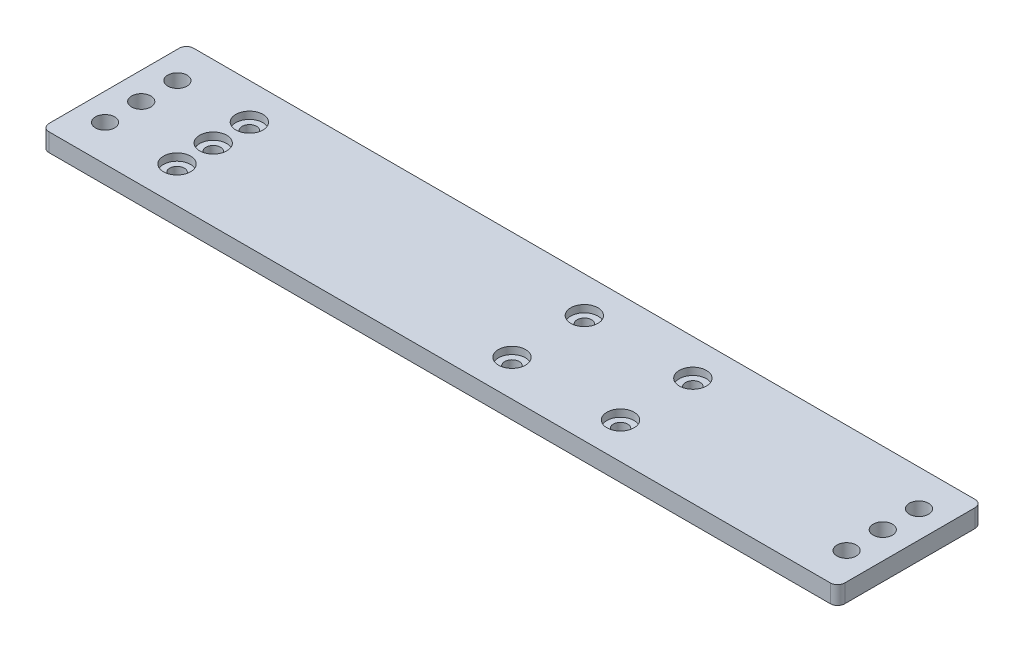
SolidWorks part; units mm, degrees
ref_plane "Front" through (0, 0, 0) normal (0, 0, 1) x (1, 0, 0)
ref_plane "Top" through (0, 0, 0) normal (0, 1, 0) x (1, 0, 0)
ref_plane "Right" through (0, 0, 0) normal (1, 0, 0) x (0, 0, -1)
sketch "Sketch1" plane through (0, 0, 0) normal (0, 1, 0) x (1, 0, 0)
  line L1 (-139.7, -25.4) -> (139.7, -25.4)
  line L2 (-139.7, -25.4) -> (-139.7, 25.4)
  line L3 (-139.7, 25.4) -> (139.7, 25.4)
  line L4 (139.7, -25.4) -> (139.7, 25.4)
  line L5 (-139.7, -25.4) -> (139.7, 25.4) construction
  line L6 (-139.7, 25.4) -> (139.7, -25.4) construction
  point P0 (0, 0)
  dimension "D1" = 50.8
  dimension "D2" = 279.4
extrude "Boss-Extrude1" add sketch "Sketch1" along normal blind 6.35
sketch "Sketch4" plane through (0, 6.35, 0) normal (0, 1, 0) x (1, 0, 0)
  line L0 (139.7, -25.4) -> (139.7, 25.4) construction
  line L1 (12.7, -12.7) -> (12.7, 12.7) construction
  line L2 (-139.7, 25.4) -> (-139.7, -25.4) construction
  line L3 (-104.902, 25.4) -> (-104.902, 12.7) construction
  line L4 (139.7, 25.4) -> (-139.7, 25.4) construction
  line L5 (-104.902, 12.7) -> (-104.902, 0) construction
  line L6 (-104.902, 0) -> (-104.902, -12.7) construction
  line L7 (-104.902, -12.7) -> (-104.902, -25.4) construction
  line L8 (-139.7, -25.4) -> (139.7, -25.4) construction
  point P0 (50.8, 12.7)
  point P2 (12.7, 12.7)
  point P4 (12.7, -12.7)
  point P6 (50.8, -12.7)
  point P23 (12.7, 0)
  point P25 (-104.902, 12.7)
  point P27 (-104.902, 0)
  point P29 (-104.902, -12.7)
  dimension "D1" = 38.1
  dimension "D2" = 88.9
  dimension "D3" = 25.4
  dimension "D4" = 34.798
hole_wizard "CBORE for #10 Socket Head Cap Screw1" positions "Sketch4" profile "Sketch3" counterbore size "#10" standard "ANSI Inch" end condition through all
sketch "Sketch3" plane through (50.8, 6.35, -12.7) normal (1, 0, 0) x (0, 0, 1)
  line L0 (0, 0) -> (0, 6.35)
  line L1 (0, 6.35) -> (2.5527, 6.35)
  line L3 (2.5527, 6.35) -> (2.5527, 2.54)
  line L4 (2.5527, 2.54) -> (4.7625, 2.54)
  line L5 (4.7625, 2.54) -> (4.7625, 0)
  line L7 (4.7625, 0) -> (0, 0)
  line L11 (0, -6.35) -> (0, 107.95) construction
  dimension "Thru Hole Dia." = 5.1054
  dimension "Thru Hole Depth" = 6.35
  dimension "C'Bore Dia." = 9.525
  dimension "C'Bore Depth" = 2.54
sketch "Sketch7" plane through (0, 0, 0) normal (0, -1, 0) x (1, 0, 0)
  line L5 (-130.175, 25.4) -> (-130.175, 12.7) construction
  line L6 (-139.7, 25.4) -> (139.7, 25.4) construction
  line L7 (-130.175, 12.7) -> (-130.175, 0) construction
  line L8 (-130.175, 0) -> (-130.175, -12.7) construction
  line L9 (-130.175, -12.7) -> (-130.175, -25.4) construction
  line L10 (139.7, -25.4) -> (-139.7, -25.4) construction
  line L12 (-139.7, -25.4) -> (-139.7, 25.4) construction
  line L13 (139.7, 25.4) -> (139.7, -25.4) construction
  point P0 (-130.175, 12.7)
  point P2 (-130.175, 0)
  point P4 (-130.175, -12.7)
  point P6 (130.175, 12.7)
  point P8 (130.175, 0)
  point P10 (130.175, -12.7)
  dimension "D1" = 9.525
  dimension "D2" = 9.525
hole_wizard "1/4 Clearance Hole1" positions "Sketch7" profile "Sketch6" hole size "1/4" standard "ANSI Inch" end condition through all
sketch "Sketch6" plane through (-130.175, 0, 12.7) normal (1, 0, 0) x (0, 0, -1)
  line L0 (0, 0) -> (0, 6.35)
  line L1 (0, 6.35) -> (3.3782, 6.35)
  line L2 (3.3782, 6.35) -> (3.3782, 0)
  line L5 (3.3782, 0) -> (0, 0)
  line L11 (0, -6.35) -> (0, 107.95) construction
  dimension "Thru Hole Dia." = 6.7564
  dimension "Thru Hole Depth" = 6.35
fillet "Fillet1" radius 2.54 4 edges at (139.7, 3.175, -25.4) (139.7, 3.175, 25.4) (-139.7, 3.175, 25.4) (-139.7, 3.175, -25.4)
